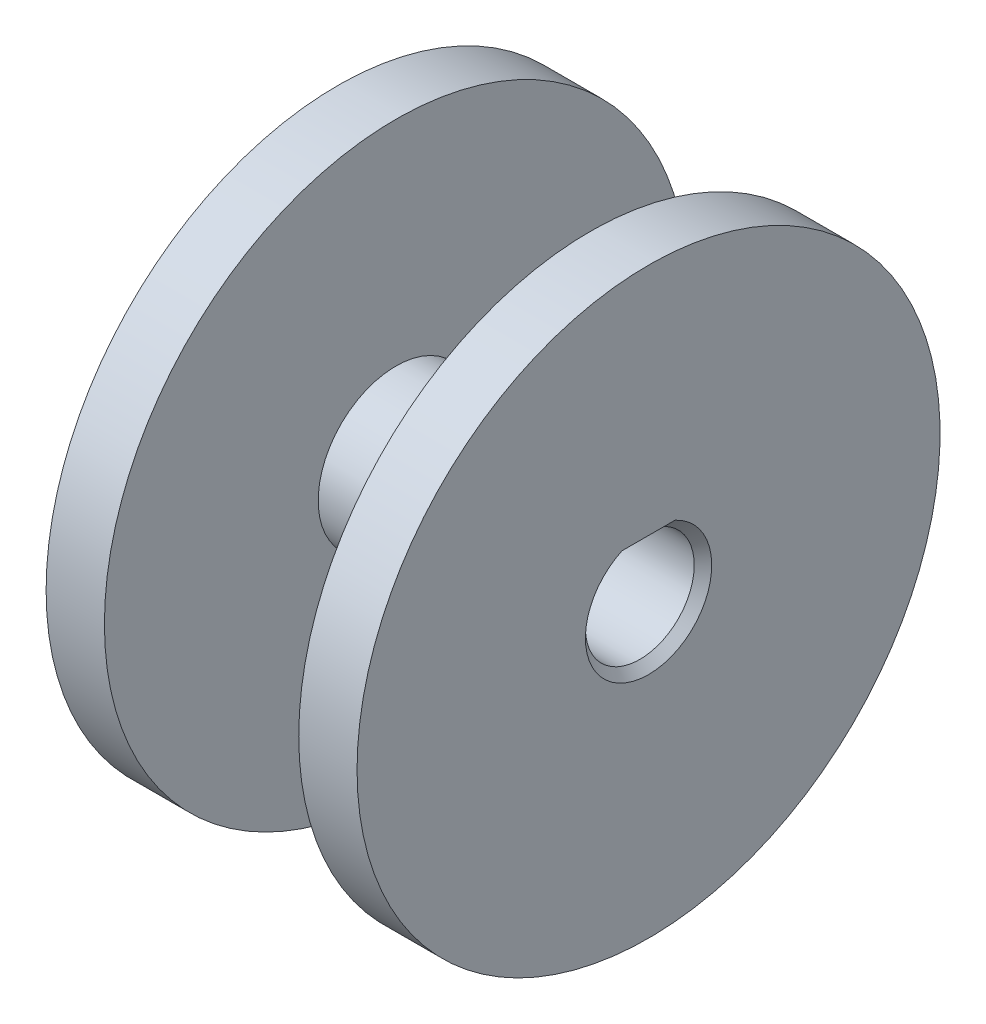
SolidWorks part; units mm, degrees
ref_plane "Front Plane" through (0, 0, 0) normal (0, 0, 1) x (1, 0, 0)
ref_plane "Top Plane" through (0, 0, 0) normal (0, 1, 0) x (1, 0, 0)
ref_plane "Right Plane" through (0, 0, 0) normal (1, 0, 0) x (0, 0, -1)
other "Center of Mass"
sketch "Sketch1" plane through (0, 0, 0) normal (1, 0, 0) x (0, 0, -1)
  line L0 (-1.3077, 2.7) -> (1.3077, 2.7) construction
  line L1 (-1.261, 2.5) -> (1.261, 2.5)
  arc A0 (-1.3077, 2.7) -> (1.3077, 2.7) centre (0, 0) ccw construction
  circle A1 centre (0, 0) radius 4
  arc A2 (-1.261, 2.5) -> (1.261, 2.5) centre (0, 0) ccw
  point P8 (0, 2.7)
  dimension "D1" = 6
  dimension "D2" = 8
  dimension "D3" = 2.6153
  dimension "D4" = 0.2
extrude "Female Shaft" add sketch "Sketch1" along normal mid plane 10
sketch "Sketch6" plane through (0, 0, 0) normal (0, 0, 1) x (1, 0, 0)
  line L2 (5, 15) -> (8, 15)
  line L3 (8, 15) -> (8, 0)
  line L4 (8, 0) -> (5, 0)
  line L5 (0, 0) -> (4.0299, 0) construction
  line L6 (5, -4) -> (5, 4) construction
  line L8 (5, 15) -> (5, 0)
  dimension "D1" = 3
  dimension "D2" = 30
revolve "Spool Edge" add sketch "Sketch6" angle 360 about L5 region at (6.5, 7.5, 0)
mirror "Spool Edge Mirror" about plane through (0, 0, 0) normal (1, 0, 0) of "Spool Edge"
extrude "Male Shaft Insert" cut sketch "Sketch1<3>" against normal through all both and the other way through all contours A0 | L1 A2 region at (0, -0.0554, 0)
sketch "Sketch1<3>" plane through (0, 0, 0) normal (1, 0, 0) x (0, 0, -1) same geometry as "Sketch1"
chamfer "Chamfer1" distance 0.45 angle 45 2 edges at (8, -2.8, 0) (8, 2.5, 0)
sketch "Sketch7" plane through (8, 0, 0) normal (1, 0, 0) x (0, 0, -1)
  circle A1 centre (0, 0) radius 5
  circle A2 centre (0, 0) radius 13
  circle A3 centre (0, 0) radius 13
  dimension "D2" = 10
  dimension "D1" = 2
